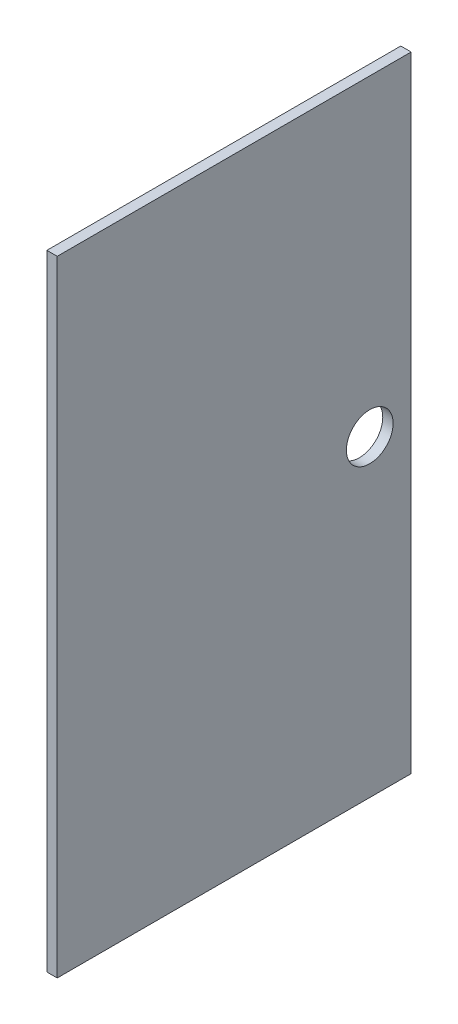
SolidWorks part; units mm, degrees
ref_plane "Front Plane" through (0, 0, 0) normal (0, 0, 1) x (1, 0, 0)
ref_plane "Top Plane" through (0, 0, 0) normal (0, 1, 0) x (1, 0, 0)
ref_plane "Right Plane" through (0, 0, 0) normal (1, 0, 0) x (0, 0, -1)
sketch "Sketch1" plane through (0, 0, 0) normal (1, 0, 0) x (0, 0, -1)
  line L1 (0, 0) -> (217.17, 0)
  line L2 (0, 0) -> (0, 383.54)
  line L3 (0, 383.54) -> (217.17, 383.54)
  line L4 (217.17, 0) -> (217.17, 383.54)
  dimension "D1" = 217.17
  dimension "D2" = 383.54
extrude "Boss-Extrude1" add sketch "Sketch1" along normal blind 6.35
sketch "Sketch2" plane through (6.35, 0, 0) normal (1, 0, 0) x (0, 0, -1)
  line L0 (0, 0) -> (217.17, 0) construction
  line L1 (217.17, 0) -> (217.17, 383.54) construction
  circle A0 centre (191.77, 191.77) radius 14.351
  dimension "D1" = 28.702
  dimension "D2" = 191.77
  dimension "D3" = 25.4
extrude "Cut-Extrude1" cut sketch "Sketch2" against normal through all both and the other way through all
